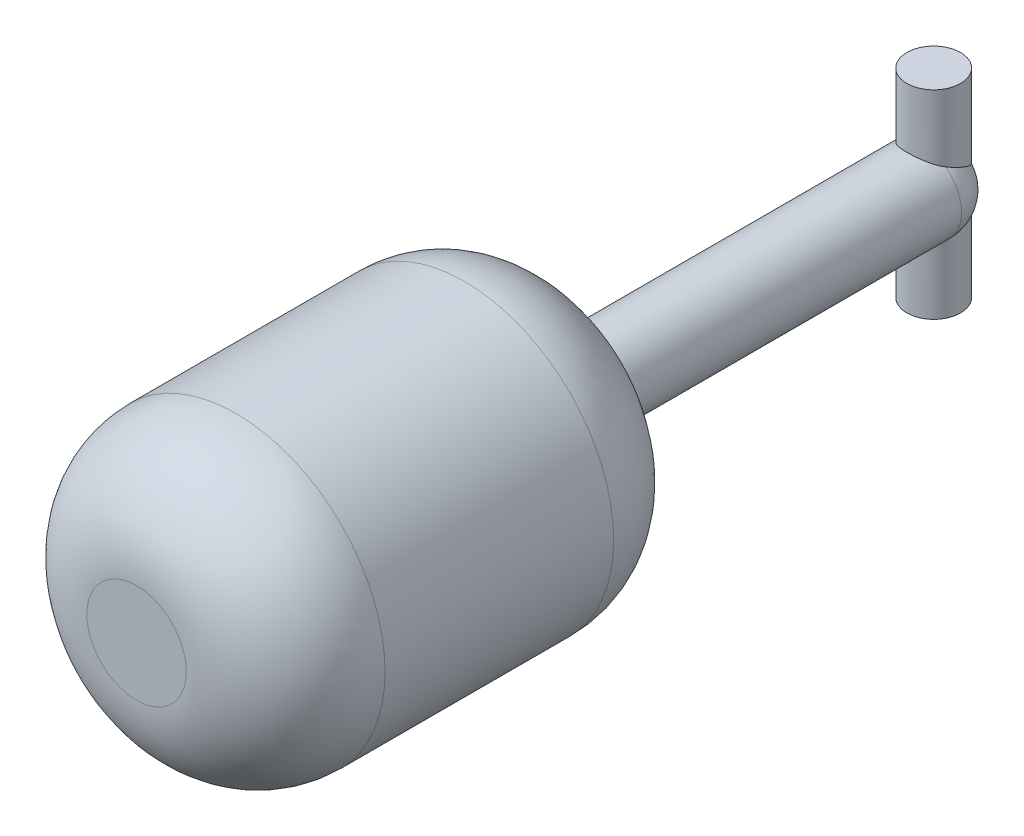
SolidWorks part; units mm, degrees
ref_plane "Спереди" through (0, 0, 0) normal (0, 0, 1) x (1, 0, 0)
ref_plane "Сверху" through (0, 0, 0) normal (0, 1, 0) x (1, 0, 0)
ref_plane "Справа" through (0, 0, 0) normal (1, 0, 0) x (0, 0, -1)
sketch "Sketch1" plane through (0, 0, 0) normal (0, 0, 1) x (1, 0, 0)
  circle A0 centre (0, 0) radius 4
  circle A1 centre (0, 0) radius 15
  circle A2 centre (0, 0) radius 12
extrude "Boss-Extrude1" add sketch "Sketch1" along normal blind 40 contours A0 region at (0, 0, 0)
extrude "Boss-Extrude2" add sketch "Sketch1<3>" along normal blind 40 from offset 40 separate body contours A1 A2 region at (-14.5757, 0, 0)
sketch "Sketch1<3>" plane through (0, 0, 0) normal (0, 0, 1) x (1, 0, 0) same geometry as "Sketch1"
extrude "Boss-Extrude3" add sketch "Sketch1<4>" along normal blind 3 from offset 40 contours A2 A0 | A0 region at (0, 0, 0) region at (-11.6606, 0, 0)
sketch "Sketch1<4>" plane through (0, 0, 0) normal (0, 0, 1) x (1, 0, 0) same geometry as "Sketch1"
fillet "Fillet1" radius 10 1 edges at (15, 0, 40)
fillet "Fillet2" radius 10 1 edges at (12, 0, 43)
extrude "Boss-Extrude4" add sketch "Sketch1<5>" along normal blind 3 from offset 80 contours A2 A0 | A1 A2 | A0 region at (0, 0, 0) region at (-14.5757, 0, 0) region at (-11.6606, 0, 0)
sketch "Sketch1<5>" plane through (0, 0, 0) normal (0, 0, 1) x (1, 0, 0) same geometry as "Sketch1"
fillet "Fillet5" radius 10 1 edges at (12, 0, 80)
fillet "Fillet6" radius 10 1 edges at (15, 0, 83)
sketch "Sketch2" plane through (0, 0, 0) normal (0, 1, 0) x (1, 0, 0)
  circle A0 centre (0, -2.8) radius 2.7
  point P2 (0, -2.768)
  point P3 (0, 0)
  point P4 (0, 0)
  point P5 (0, 0)
  point P6 (0, 0)
extrude "Boss-Extrude5" add sketch "Sketch2" along normal blind 10 and the other way blind 10
fillet "Fillet7" radius 4 1 edges at (4, 0, 0)
